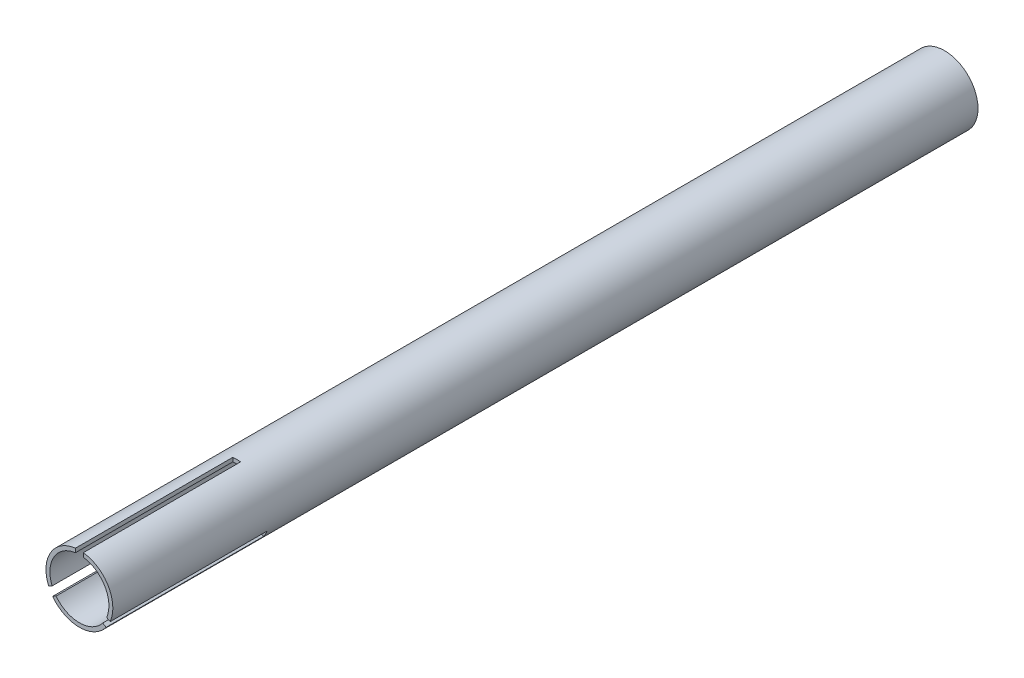
SolidWorks part; units mm, degrees
material "Corrugated Paper"
ref_plane "Front Plane" through (0, 0, 0) normal (0, 0, 1) x (1, 0, 0)
ref_plane "Top Plane" through (0, 0, 0) normal (0, 1, 0) x (1, 0, 0)
ref_plane "Right Plane" through (0, 0, 0) normal (1, 0, 0) x (0, 0, -1)
sketch "Sketch1" plane through (0, 0, 0) normal (0, 0, 1) x (1, 0, 0)
  circle A0 centre (0, 0) radius 19.05
  circle A1 centre (0, 0) radius 21.59
  dimension "D1" = 43.18
  dimension "D2" = 38.1
extrude "Boss-Extrude1" add sketch "Sketch1" along normal blind 558.8
sketch "Sketch2" plane through (0, 0, 0) normal (0, 1, 0) x (1, 0, 0)
  line L0 (-21.59, -558.8) -> (21.59, -558.8) construction
  line L1 (-2.54, -558.8) -> (2.54, -558.8)
  line L2 (-2.54, -558.8) -> (-2.54, -457.2)
  line L3 (-2.54, -457.2) -> (2.54, -457.2)
  line L4 (2.54, -558.8) -> (2.54, -457.2)
  point P6 (0, -558.8)
  dimension "D1" = 5.08
  dimension "D2" = 101.6
extrude "Cut-Extrude1" cut sketch "Sketch2" along normal up to next
ref_axis "Axis1" through (0, 0, -27.94) along (0, 0, 1)
pattern_circular "CirPattern1" count 3 every 120 about axis through (0, 0, -27.94) along (0, 0, 1) of "Cut-Extrude1"
